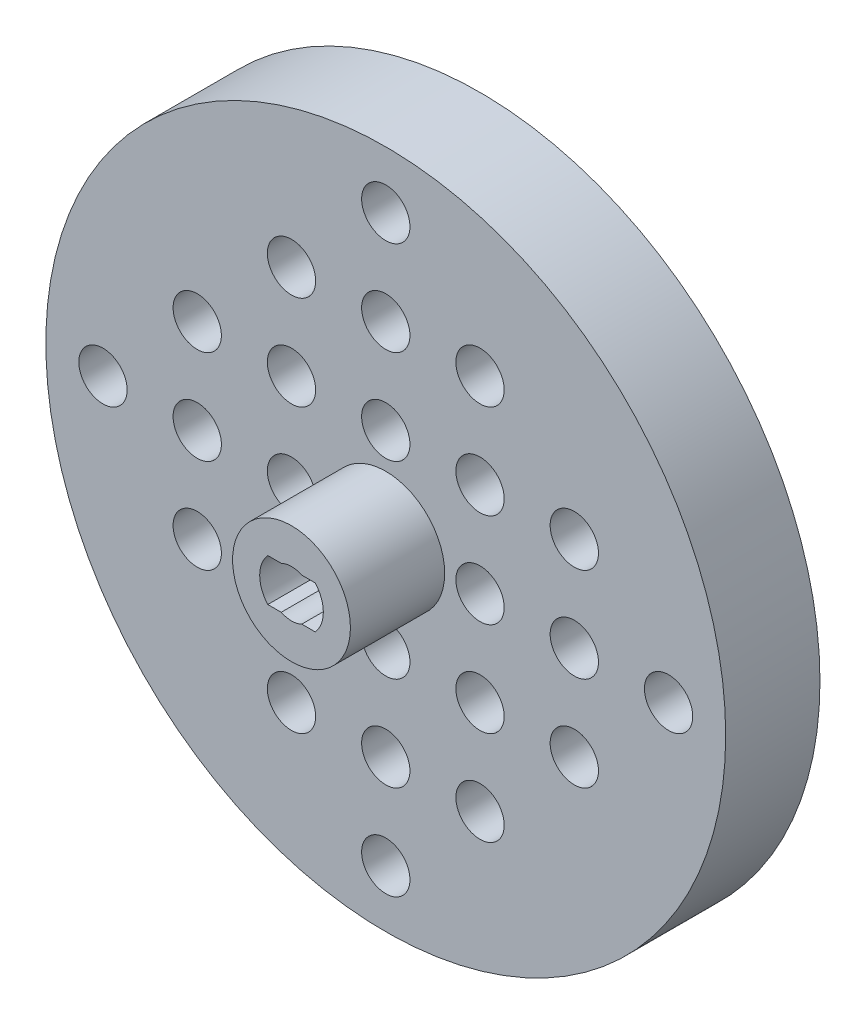
SolidWorks part; units mm, degrees
material "ABS"
ref_plane "Front" through (0, 0, 0) normal (0, 0, 1) x (1, 0, 0)
ref_plane "Top" through (0, 0, 0) normal (0, 1, 0) x (1, 0, 0)
ref_plane "Right" through (0, 0, 0) normal (1, 0, 0) x (0, 0, -1)
sketch "Эскиз1" plane through (0, 0, 0) normal (0, 0, 1) x (1, 0, 0)
  circle A0 centre (0, 0) radius 28.85
  dimension "D1" = 57.7
extrude "Бобышка-Вытянуть1" add sketch "Эскиз1" along normal blind 4 and the other way blind 4
sketch "Эскиз2" plane through (0, 0, 4) normal (0, 0, 1) x (1, 0, 0)
  circle A0 centre (0, 0) radius 5
extrude "Бобышка-Вытянуть2" add sketch "Эскиз2" along normal blind 8
sketch "Эскиз3" plane through (0, 0, 12) normal (0, 0, 1) x (1, 0, 0)
  circle A0 centre (0, 0) radius 1.8
  dimension "D1" = 3.6
extrude "Вырез-Вытянуть1" cut sketch "Эскиз3" against normal through all
sketch "Эскиз4" plane through (0, 0, -4) normal (0, 0, -1) x (-1, 0, 0)
  circle A0 centre (0, 0) radius 4
extrude "Вырез-Вытянуть2" cut sketch "Эскиз4" against normal blind 4
sketch "Эскиз5" plane through (0, 0, -4) normal (0, 0, -1) x (-1, 0, 0)
  circle A0 centre (0, 0) radius 5
extrude "Вырез-Вытянуть3" cut sketch "Эскиз5" against normal blind 0.7
sketch "Эскиз6" plane through (0, 0, 12) normal (0, 0, 1) x (1, 0, 0)
  line L1 (2.0125, 1.8) -> (0.8718, 1.8)
  line L2 (0, 0) -> (1.0748, 0) construction
  line L3 (2.0125, -1.8) -> (0.8718, -1.8)
  line L4 (-0.8718, -1.8) -> (-2.0125, -1.8)
  line L5 (-0.8718, 1.8) -> (-2.0125, 1.8)
  circle A0 centre (0, 0) radius 2
  arc A1 (-2.0125, 1.8) -> (-2.0125, -1.8) centre (0, 0) ccw
  arc A2 (2.0125, -1.8) -> (2.0125, 1.8) centre (0, 0) ccw
  point P12 (0, -1.8)
  circle M10 centre (0, 0) radius 1.8
  dimension "D1" = 2.7
  dimension "D2" = 4
  dimension "D3" = 3.6
  dimension "D4" = 1.8
extrude "Вырез-Вытянуть4" cut sketch "Эскиз6" against normal blind 7.5 contours L2 M10 | L2 A1 L4 A0 | L2 A0 M10 | A1 L2 A0 L5 | A0 L2 M10 | A0 L2 A2 L1 | L2 A0 L3 A2 | L2 M10 region at (2.0464, 0, 12) region at (1.6467, 1.0321, 12) region at (-2.0464, 0, 12) region at (-1.7491, 0, 12)
sketch "Эскиз7" plane through (0, 0, 0) normal (0, 0, 1) x (1, 0, 0)
  line L0 (0, 0) -> (-8, 0) construction
  line L1 (-8, 0) -> (-16, 0) construction
  line L2 (-16, 0) -> (-24, 0) construction
  line L3 (-24, 0) -> (-24, 8) construction
  line L4 (-24, 8) -> (-24, 16) construction
  line L5 (-24, 16) -> (-24, 24) construction
  line L6 (-24, 16) -> (8.535, 16) construction
  line L7 (-24, 24) -> (8.535, 24) construction
  line L8 (-24, 8) -> (8.535, 8) construction
  line L9 (-24, 0) -> (8.535, 0) construction
  line L10 (0, 0) -> (0, 30.3632) construction
  line L11 (-8, 0) -> (-8, 30.3632) construction
  line L12 (-16, 0) -> (-16, 30.3632) construction
  line L13 (-24, 0) -> (-24, 30.3632) construction
  line L14 (-24, -16) -> (-24, -24) construction
  line L15 (-24, -8) -> (-24, -16) construction
  line L16 (24, -8) -> (24, -16) construction
  line L17 (24, 16) -> (24, 24) construction
  line L18 (24, 8) -> (24, 16) construction
  line L19 (24, 0) -> (24, 8) construction
  line L20 (16, 0) -> (24, 0) construction
  line L21 (8, 0) -> (16, 0) construction
  circle A0 centre (-24, 0) radius 2.05
  circle A1 centre (-16, 0) radius 2.05
  circle A2 centre (-8, 0) radius 2.05
  circle A3 centre (-8, 8) radius 2.05
  circle A4 centre (-16, 8) radius 2.05
  circle A5 centre (0, 8) radius 2.05
  circle A6 centre (0, 16) radius 2.05
  circle A7 centre (-8, 16) radius 2.05
  circle A8 centre (0, 24) radius 2.05
  circle A9 centre (0, -24) radius 2.05
  circle A10 centre (-8, -16) radius 2.05
  circle A11 centre (0, -16) radius 2.05
  circle A12 centre (0, -8) radius 2.05
  circle A13 centre (-16, -8) radius 2.05
  circle A14 centre (-8, -8) radius 2.05
  circle A15 centre (8, -8) radius 2.05
  circle A16 centre (16, -8) radius 2.05
  circle A17 centre (8, -16) radius 2.05
  circle A18 centre (8, 16) radius 2.05
  circle A19 centre (16, 8) radius 2.05
  circle A20 centre (8, 8) radius 2.05
  circle A21 centre (8, 0) radius 2.05
  circle A22 centre (16, 0) radius 2.05
  circle A23 centre (24, 0) radius 2.05
  dimension "D1" = 8
  dimension "D2" = 8
  dimension "D3" = 8
  dimension "D4" = 8
  dimension "D5" = 8
  dimension "D6" = 8
extrude "Вырез-Вытянуть5" cut sketch "Эскиз7" against normal through all both and the other way through all
